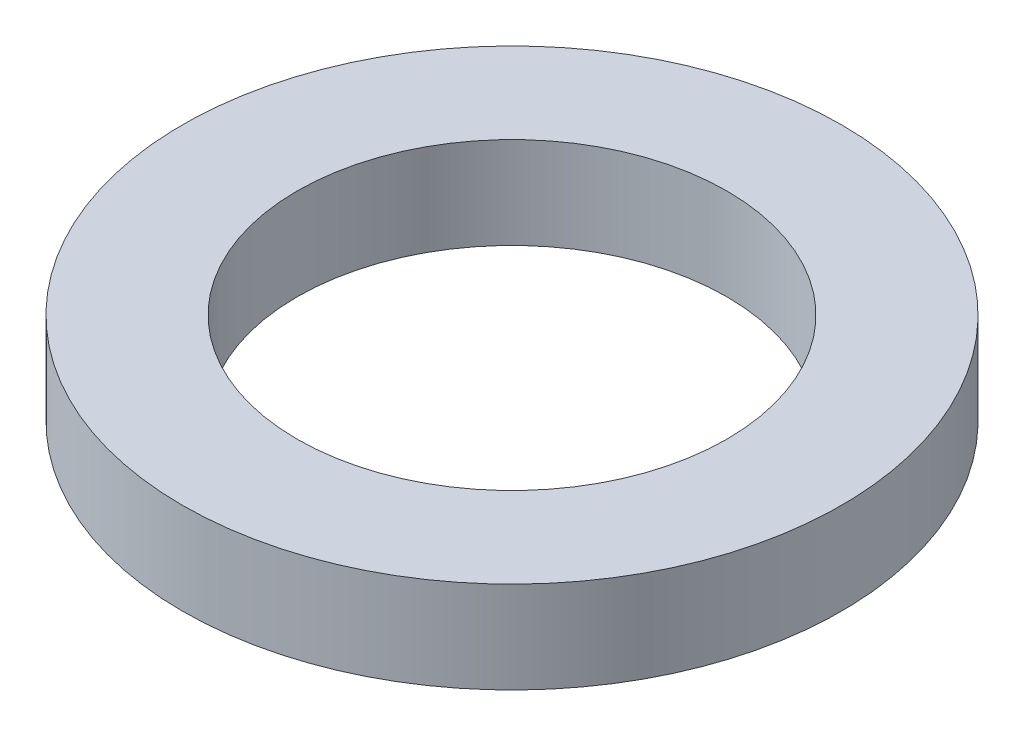
SolidWorks part; units mm, degrees
ref_plane "Front Plane" through (0, 0, 0) normal (0, 0, 1) x (1, 0, 0)
ref_plane "Top Plane" through (0, 0, 0) normal (0, 1, 0) x (1, 0, 0)
ref_plane "Right Plane" through (0, 0, 0) normal (1, 0, 0) x (0, 0, -1)
sketch "Sketch1" plane through (0, 0, 0) normal (0, 1, 0) x (1, 0, 0)
  circle A0 centre (0, 0) radius 57.5
  dimension "FLANGE_OD" = 115
extrude "Boss-Extrude1" add sketch "Sketch1" along normal blind 16
sketch "Sketch2" plane through (0, 0, 0) normal (0, 1, 0) x (1, 0, 0)
  circle A0 centre (0, 0) radius 37.5
  dimension "BORE_D" = 75
extrude "Cut-Extrude1" cut sketch "Sketch2" along normal through all
sketch "Sketch3" plane through (0, 16, 0) normal (0, 1, 0) x (1, 0, 0)
  circle A0 centre (0, 0) radius 22.2079 construction
  circle A1 centre (-22.2079, 0) radius 3.5826
  dimension "BOLT_D" = 7.1651
  dimension "BOLT_PCD" = 44.4158
extrude "Cut-Extrude2" cut sketch "Sketch3" against normal blind 10.9869 rebuild error yes
pattern_circular "CirPattern1" count 8 over 360 rebuild error yes
